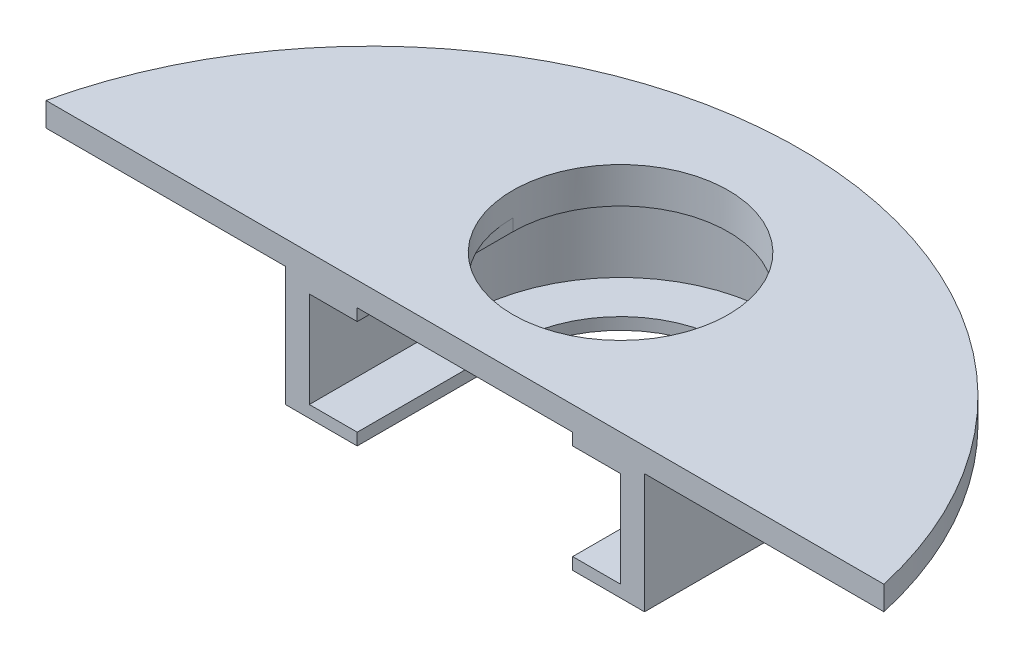
SolidWorks part; units mm, degrees
ref_plane "Front Plane" through (0, 0, 0) normal (0, 0, 1) x (1, 0, 0)
ref_plane "Top Plane" through (0, 0, 0) normal (0, 1, 0) x (1, 0, 0)
ref_plane "Right Plane" through (0, 0, 0) normal (1, 0, 0) x (0, 0, -1)
sketch "Sketch1" plane through (0, 0, 0) normal (0, 1, 0) x (1, 0, 0)
  line L0 (-13, 0) -> (-13, -13)
  line L1 (13, 0) -> (13, -13)
  line L2 (15, 0) -> (15, -13)
  line L3 (-15, 0) -> (-15, -13)
  line L4 (-35, -13) -> (35, -13)
  line L5 (-9, 0) -> (-9, -13)
  line L6 (9, 0) -> (9, -13)
  circle A0 centre (0, 0) radius 13 construction
  circle A2 centre (0, 0) radius 15 construction
  arc A3 (13, 0) -> (-13, 0) centre (0, 0) ccw
  arc A4 (15, 0) -> (-15, 0) centre (0, 0) ccw
  arc A5 (-35, -13) -> (35, -13) centre (0, -20.875) cw
  arc A6 (-32.9469, -13) -> (32.9469, -13) centre (0, -20.875) cw
  circle A7 centre (0, 0) radius 9
  dimension "D1" = 26
  dimension "D2" = 2
  dimension "D7" = 18
  dimension "D3" = 13
  dimension "D5" = 20
  dimension "D6" = 20
  dimension "D4" = 2
extrude "Boss-Extrude1" add sketch "Sketch1" along normal blind 2 contours A6 L4 L3 A4 | A6 A4 L2 L4 | L1 A3 L0 L4 A7 | A6 A3 L1 L4 L2 A4 | A6 A4 L3 L4 L0 A3 | A4 A6 | L4 A6 A4 A5 | A4 A6 L4 A5 | A5 L4 | A7 region at (-8.9324, 0, -8.9324) region at (-13.3002, 0, 6.5) region at (4.7242, 0, -12.3658) region at (0, 0, -13.5358) region at (-21.4914, 0, 3.7909) region at (-24.8424, 0, -2.8091) region at (21.4914, 0, 3.7909) region at (5.1556, 0, -14.5625)
extrude "Boss-Extrude3" add sketch "Sketch1<5>" against normal blind 9 contours A6 A3 L1 L4 L2 A4 | A4 A6 | A6 A4 L3 L4 L0 A3 region at (-13.3002, 0, 6.5) region at (4.7242, 0, -12.3658) region at (0, 0, -13.5358)
sketch "Sketch1<5>" plane through (0, 0, 0) normal (0, 1, 0) x (1, 0, 0) same geometry as "Sketch1"
extrude "Boss-Extrude4" add sketch "Sketch1<6>" against normal blind 1 contours A7 L6 L4 L1 A3 L0 L5 region at (-8.9324, 0, -8.9324)
sketch "Sketch1<6>" plane through (0, 0, 0) normal (0, 1, 0) x (1, 0, 0) same geometry as "Sketch1"
extrude "Boss-Extrude5" add sketch "Sketch1<7>" against normal blind 1 from surface contours A6 A4 L3 L4 L0 A3 | A4 A6 | A6 A3 L1 L4 L2 A4 | A7 L6 L4 L1 A3 L0 L5 region at (-8.9324, 0, -8.9324) region at (-13.3002, 0, 6.5) region at (4.7242, 0, -12.3658) region at (0, 0, -13.5358) starting at face at (0, -9, 3)
sketch "Sketch1<7>" plane through (0, 0, 0) normal (0, 1, 0) x (1, 0, 0) same geometry as "Sketch1"
